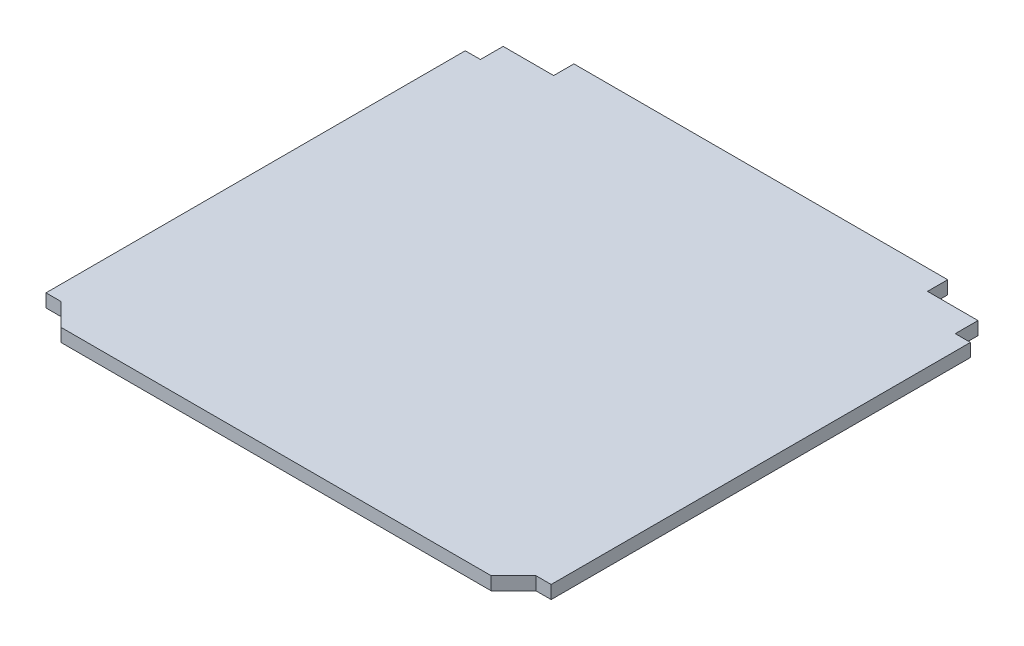
SolidWorks part; units mm, degrees
ref_plane "Front Plane" through (0, 0, 0) normal (0, 0, 1) x (1, 0, 0)
ref_plane "Top Plane" through (0, 0, 0) normal (0, 1, 0) x (1, 0, 0)
ref_plane "Right Plane" through (0, 0, 0) normal (1, 0, 0) x (0, 0, -1)
sketch "Sketch2" plane through (0, 0, 0) normal (0, 1, 0) x (1, 0, 0)
  line L0 (37, 50) -> (-37, 50) construction
  line L1 (50, 50) -> (-50, 50)
  line L2 (50, 50) -> (50, -50)
  line L3 (50, -50) -> (-50, -50)
  line L4 (-50, 50) -> (-50, -50)
  line L5 (-50, -41.5) -> (-50, 41.5) construction
  line L6 (50, 41.5) -> (50, -41.5) construction
  line L7 (37, 50) -> (37, 46)
  line L8 (37, 46) -> (46, 46)
  line L9 (46, 46) -> (47, 46)
  line L10 (47, 46) -> (47, 41.5)
  line L11 (47, 41.5) -> (50.0658, 41.5)
  line L13 (0, 70.3951) -> (0, -61.0345) construction
  line L15 (-84.1689, 0) -> (95.4998, 0) construction
  line L16 (-37, 50) -> (-37, 46)
  line L17 (-37, 46) -> (-46, 46)
  line L18 (-46, 46) -> (-47, 46)
  line L19 (-47, 46) -> (-47, 41.5)
  line L20 (-47, 41.5) -> (-50.0658, 41.5)
  line L21 (18.75, -50) -> (13.25, -50) construction
  line L22 (-37, -50) -> (-37, -47)
  line L23 (-37, -47) -> (-41.5, -47)
  line L24 (-41.5, -47) -> (-47, -41.5)
  line L25 (-47, -41.5) -> (-50, -41.5)
  line L26 (37, -50) -> (37, -47)
  line L27 (37, -47) -> (41.5, -47)
  line L28 (41.5, -47) -> (47, -41.5)
  line L29 (47, -41.5) -> (50, -41.5)
  line L30 (-50, -45.9311) -> (50, -45.9311)
extrude "Boss-Extrude1" add sketch "Sketch2" along normal up to surface (2.6 mm away) contours L11 L10 L9 L8 L7 L1 L4 L3 L2 region at (0, 0, -1.6332)
